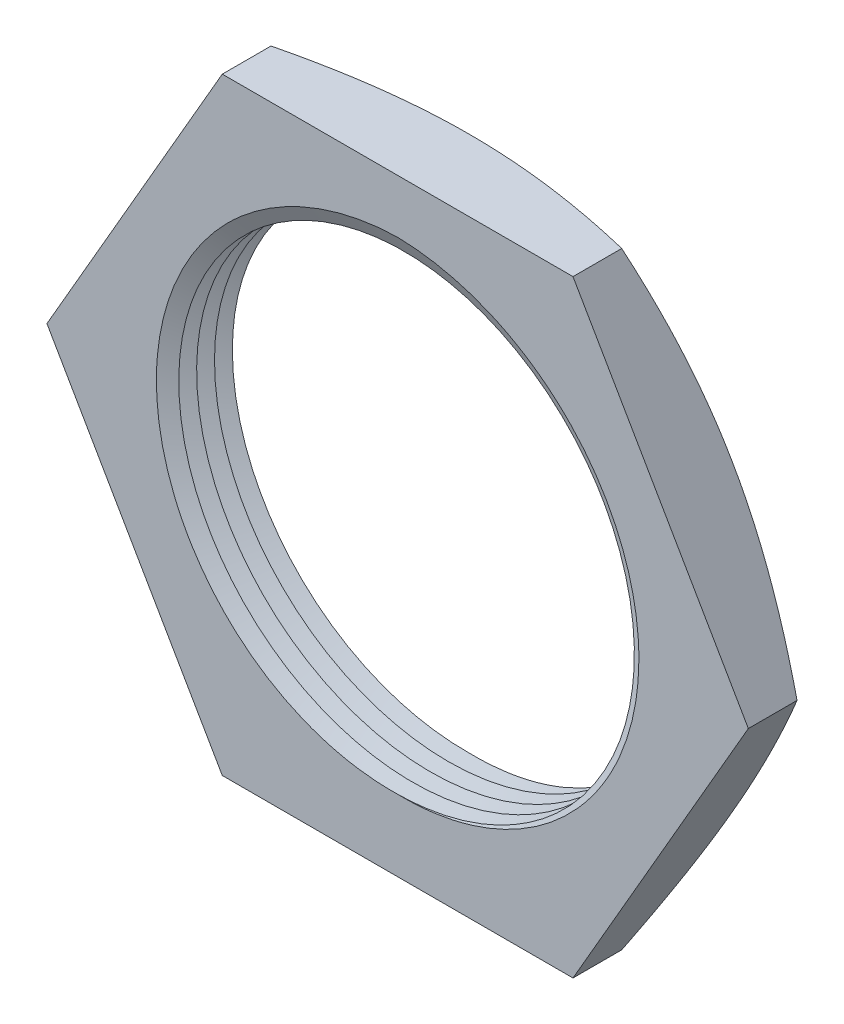
SolidWorks part; units mm, degrees
ref_plane "Piano frontale" through (0, 0, 0) normal (0, 0, 1) x (1, 0, 0)
ref_plane "Piano superiore" through (0, 0, 0) normal (0, 1, 0) x (1, 0, 0)
ref_plane "Piano destro" through (0, 0, 0) normal (1, 0, 0) x (0, 0, -1)
sketch "Schizzo1" plane through (0, 0, 0) normal (0, 0, 1) x (1, 0, 0)
  line L6 (-9.815, -17) -> (9.815, -17)
  line L7 (-19.6299, 0) -> (-9.815, -17)
  line L8 (-9.815, 17) -> (-19.6299, 0)
  line L9 (9.815, 17) -> (-9.815, 17)
  line L10 (19.6299, 0) -> (9.815, 17)
  line L11 (9.815, -17) -> (19.6299, 0)
  circle A1 centre (0, 0) radius 13
  point P10 (0, 0)
  point P23 (0, 0)
  dimension "D1" = 34
  dimension "D4" = 26
  dimension "D2" = 17
  dimension "D3" = 6
extrude "Estrusione-Estrusione1" add sketch "Schizzo1" along normal blind 4
sketch "Schizzo2" plane through (0, 0, 0) normal (1, 0, 0) x (0, 0, -1)
  line L1 (-0.5, 13) -> (-0.5, 12.7055)
  line L2 (0, 14) -> (0.5, 13)
  line L3 (0, 14) -> (-0.5, 13)
  line L4 (-0.5, 12.7055) -> (0.5, 12.7055)
  line L5 (0.5, 12.7055) -> (0.5, 13)
  line L6 (0.5, 13) -> (-0.5, 13) construction
  line L7 (0, 14) -> (0, 13) construction
  line L8 (-0.5, 13) -> (-0.5, 14) construction
  line L9 (-0.5, 14) -> (0, 14) construction
  dimension "D1" = 1
  dimension "D2" = 0.2945
  dimension "D3" = 1
  dimension "D4" = 53.13
  dimension "D5" = 13
sketch "Schizzo3" plane through (0, 0, 0) normal (0, 0, 1) x (1, 0, 0)
  circle A0 centre (0, 0) radius 13
curve "Elica/Spirale1" pitch 1 height 6 turns 6
sweep "Taglia-Sweep1" cut profiles "Schizzo2" path "Elica/Spirale1" align with end faces yes
sketch "Schizzo4" plane through (0, 0, 0) normal (0, 1, 0) x (1, 0, 0)
  line L3 (17, 0) -> (13, 0) construction
  line L4 (0, 0) -> (0, -8.0028) construction
  line L5 (17, 0) -> (21.1299, -2)
  line L6 (21.1299, -2) -> (25.2598, -4)
  line L7 (25.2598, -4) -> (25.2598, 1.264)
  line L8 (25.2598, 1.264) -> (17, 1.264)
  line L9 (17, 1.264) -> (17, 0)
  dimension "D1" = 25.84
  dimension "D2" = 4
  dimension "D3" = 13
revolve "Taglia-Rivoluzione1" cut sketch "Schizzo4" angle 360 about L4
sketch "Schizzo6" plane through (0, 0, 0) normal (1, 0, 0) x (0, 0, -1)
  line L0 (0, 0) -> (-8.4317, 0) construction
